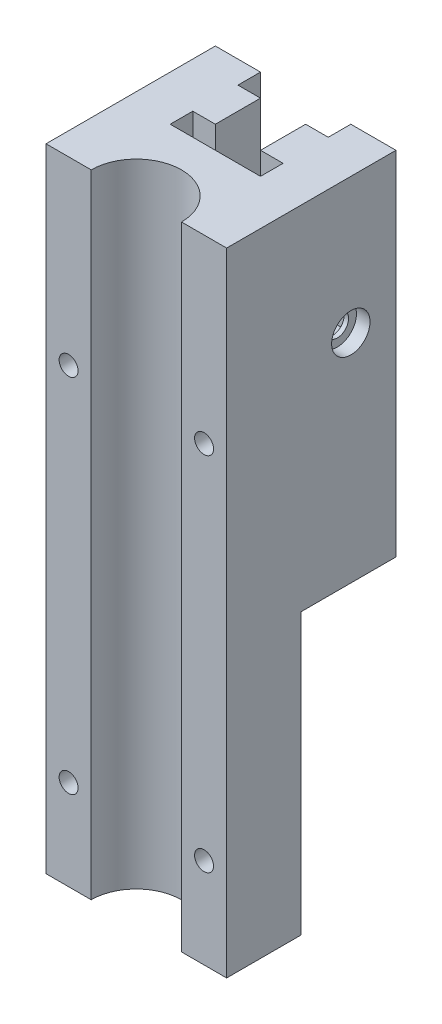
SolidWorks part; units mm, degrees
other "Markup1"
sketch "Sketch9" plane through (-20, 0, 37.5) normal (-0.6467, 0.1839, 0.7403) x (0.76, 0.0728, 0.6458)
ref_plane "Front Plane" through (0, 0, 0) normal (0, 0, 1) x (1, 0, 0)
ref_plane "Top Plane" through (0, 0, 0) normal (0, 1, 0) x (1, 0, 0)
ref_plane "Right Plane" through (0, 0, 0) normal (1, 0, 0) x (0, 0, -1)
sketch "Sketch1" plane through (0, 0, 0) normal (0, 1, 0) x (1, 0, 0)
  line L0 (10, 0) -> (-10, 0) construction
  line L1 (-10, 0) -> (-20, 0)
  line L2 (-20, 0) -> (-20, -37.5)
  line L3 (-20, -37.5) -> (20, -37.5)
  line L4 (20, -37.5) -> (20, 0)
  line L5 (20, 0) -> (10, 0)
  line L6 (10, 0) -> (10, -5)
  line L7 (10, -5) -> (5, -5)
  line L8 (5, -5) -> (5, -15)
  line L9 (5, -15) -> (10, -15)
  line L10 (10, -15) -> (10, -20)
  line L11 (10, -20) -> (-10, -20)
  line L12 (0, 0) -> (0, -20) construction
  line L13 (-10, 0) -> (-10, -5)
  line L14 (-10, -5) -> (-5, -5)
  line L15 (-5, -5) -> (-5, -15)
  line L16 (-5, -15) -> (-10, -15)
  line L17 (-10, -15) -> (-10, -20)
  line L18 (0, 0) -> (0, -37.5) construction
  circle A1 centre (0, -37.5) radius 10
  point P3 (0, 0)
  dimension "D10" = 20
  dimension "D1" = 37.5
  dimension "D2" = 5
  dimension "D3" = 5
  dimension "D4" = 5
  dimension "D5" = 10
  dimension "D6" = 5
  dimension "D7" = 10
  dimension "D8" = 40
  dimension "D9" = 20
  dimension "D11" = 37.5
extrude "Boss-Extrude1" add sketch "Sketch1" against normal blind 140 contours A1 L3 L4 L5 L6 L7 L8 L9 L10 L11 L17 L16 L15 L14 L13 L1 L2 region at (-10.5483, 0, 2.5)
sketch "Sketch5" plane through (0, -140, 0) normal (0, -1, 0) x (1, 0, 0)
  line L0 (-20, 0) -> (-20, 37.5) construction
  line L1 (20, 0) -> (-20, 0)
  line L2 (20, 0) -> (20, 21)
  line L3 (20, 21) -> (-20, 21)
  line L4 (-20, 0) -> (-20, 21)
  dimension "D1" = 21
extrude "Cut-Extrude5" cut sketch "Sketch5" against normal blind 62
sketch "Sketch3" plane through (20, 0, 0) normal (1, 0, 0) x (0, 0, -1)
  line L0 (0, -78) -> (0, 0) construction
  line L1 (0, 0) -> (-20, 0)
  line L2 (0, 0) -> (0, -25)
  line L3 (0, -25) -> (-20, -25)
  line L4 (-20, 0) -> (-20, -25)
  line L5 (-20, -25) -> (0, -25)
  line L6 (-20, -25) -> (-20, -35)
  line L7 (-20, -35) -> (0, -35)
  line L8 (0, -25) -> (0, -35)
  line L9 (-15, -25) -> (-15, -35)
  line L10 (-5, -25) -> (-5, -35)
  line L11 (-10, -25) -> (-10, -35) construction
  line L12 (-15, -30) -> (-5, -30) construction
  line L13 (-37.5, 0) -> (0, 0) construction
  circle A0 centre (-10, -30) radius 2.5
  circle A1 centre (-10, -30) radius 4.25
  dimension "D6" = 5
  dimension "D7" = 8.5
  dimension "D1" = 20
  dimension "D2" = 0
  dimension "D3" = 10
  dimension "D4" = 5
  dimension "D5" = 10
  dimension "D9" = 25
extrude "Cut-Extrude2" cut sketch "Sketch3" against normal blind 30 and the other way blind 1 from offset 5 contours L10 L5 L9 L7 | A1 A0 | A0 region at (20, -30, 5.1414) region at (20, -30, 10) region at (20, -30, 14.1298) offset against normal yes
extrude "Cut-Extrude3" cut sketch "Sketch3<3>" against normal through all contours A0 region at (20, -30, 10)
sketch "Sketch3<3>" plane through (20, 0, 0) normal (1, 0, 0) x (0, 0, -1) same geometry as "Sketch3"
extrude "Cut-Extrude4" cut sketch "Sketch3<5>" against normal blind 3 contours A1 A0 region at (20, -30, 14.1298)
sketch "Sketch3<5>" plane through (20, 0, 0) normal (1, 0, 0) x (0, 0, -1) same geometry as "Sketch3"
mirror "Mirror1" about plane through (0, 0, 0) normal (1, 0, 0) of "Cut-Extrude4"
sketch "Sketch7" plane through (0, 0, 37.5) normal (0, 0, 1) x (1, 0, 0)
  line L0 (-20, -140) -> (-10, -140) construction
  line L1 (-10, -140) -> (-10, 0) construction
  line L2 (10, -140) -> (20, -140) construction
  line L3 (10, -140) -> (10, 0) construction
  line L4 (20, -140) -> (20, 0) construction
  line L5 (10, 0) -> (20, 0) construction
  line L6 (-20, 0) -> (-10, 0) construction
  line L7 (-20, -140) -> (-20, 0) construction
  line L8 (-20, -140) -> (-10, -140)
  line L9 (-10, -140) -> (-10, 0)
  line L10 (10, -140) -> (20, -140)
  line L11 (10, -140) -> (10, 0)
  line L12 (20, -140) -> (20, 0)
  line L13 (10, 0) -> (20, 0)
  line L14 (-20, 0) -> (-10, 0)
  line L15 (-20, -140) -> (-20, 0)
  line L16 (0, -140) -> (0, 0) construction
  line L17 (-10, 0) -> (10, 0)
  line L18 (-10, 0) -> (-10, -140)
  line L19 (-10, -140) -> (10, -140)
  line L20 (10, 0) -> (10, -140)
  line L21 (-15, 0) -> (-15, -140) construction
  line L22 (15, 0) -> (15, -140) construction
  circle A0 centre (-15, -120) radius 2.1
  circle A1 centre (15, -120) radius 2.1
  circle A2 centre (-15, -40) radius 2.1
  circle A3 centre (15, -40) radius 2.1
  dimension "D1" = 4.2
  dimension "D2" = 4.2
  dimension "D7" = 4.2
  dimension "D8" = 4.2
  dimension "D3" = 20
  dimension "D4" = 20
  dimension "D5" = 40
  dimension "D6" = 40
extrude "Cut-Extrude7" cut sketch "Sketch7" against normal blind 10 contours A2 | A3 | A1 | A0
